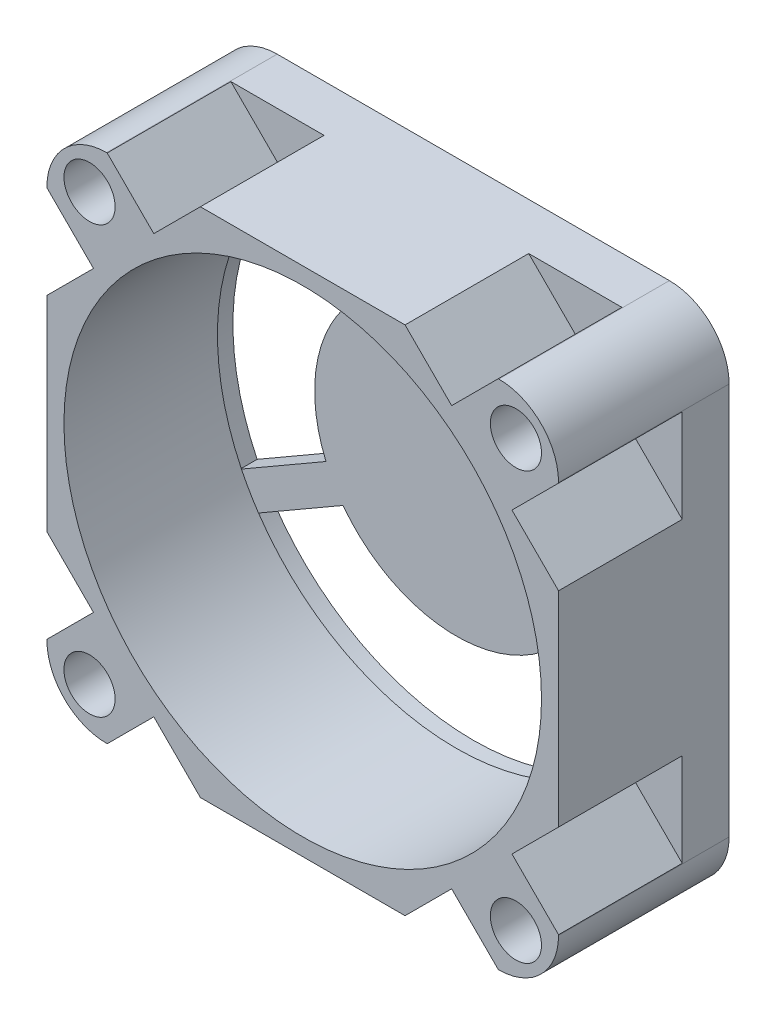
SolidWorks part; units mm, degrees
ref_plane "Płaszczyzna przednia" through (0, 0, 0) normal (0, 0, 1) x (1, 0, 0)
ref_plane "Płaszczyzna górna" through (0, 0, 0) normal (0, 1, 0) x (1, 0, 0)
ref_plane "Płaszczyzna prawa" through (0, 0, 0) normal (1, 0, 0) x (0, 0, -1)
sketch "Sketch1" plane through (0, 0, 0) normal (0, 0, 1) x (1, 0, 0)
  line L1 (0, 0) -> (30, 0)
  line L2 (0, 0) -> (0, 30)
  line L3 (0, 30) -> (30, 30)
  line L4 (30, 0) -> (30, 30)
  dimension "D1" = 30
extrude "Boss-Extrude1" add sketch "Sketch1" along normal blind 10
sketch "Sketch2" plane through (0, 0, 10) normal (0, 0, 1) x (1, 0, 0)
  line L0 (0, 30) -> (30, 0) construction
  line L1 (0, 0) -> (30, 30) construction
  circle A0 centre (15, 15) radius 14
  point P11 (15, 15)
  dimension "D1" = 28
extrude "Cut-Extrude1" cut sketch "Sketch2" against normal blind 9
sketch "Sketch3" plane through (0, 0, 1) normal (0, 0, 1) x (1, 0, 0)
  line L0 (14, 23.2395) -> (14, 29.0554)
  line L1 (16, 23.2395) -> (16, 29.0554)
  line L2 (22.6356, 11.7463) -> (27.6724, 8.8383)
  line L3 (21.6356, 10.0142) -> (26.6724, 7.1063)
  line L4 (8.3644, 10.0142) -> (3.3276, 7.1063)
  line L5 (7.3644, 11.7463) -> (2.3276, 8.8383)
  line L8 (0, 30) -> (0, 0) construction
  line L9 (30, 0) -> (30, 30) construction
  arc A0 (3.3276, 7.1063) -> (26.6724, 7.1063) centre (15, 15) ccw
  arc A1 (8.3644, 10.0142) -> (21.6356, 10.0142) centre (15, 15) ccw
  arc A2 (14, 23.2395) -> (7.3644, 11.7463) centre (15, 15) ccw
  arc A3 (14, 29.0554) -> (2.3276, 8.8383) centre (15, 15) ccw
  arc A4 (22.6356, 11.7463) -> (16, 23.2395) centre (15, 15) ccw
  arc A5 (27.6724, 8.8383) -> (16, 29.0554) centre (15, 15) ccw
  dimension "D1" = 16.6
  dimension "D2" = 2
  dimension "D4" = 14
  dimension "D5" = 14
  dimension "D3" = 3
extrude "Cut-Extrude2" cut sketch "Sketch3" against normal through all
hole_wizard "Ø3.0mm Dowel Hole1" positions "Sketch4" profile "Sketch5" hole size "Ø3.0" standard "ANSI Metric" end condition through all
sketch "Sketch4" plane through (0, 0, 0) normal (0, 0, -1) x (-1, 0, 0)
  line L0 (-30, 0) -> (-30, 30) construction
  line L2 (-30, 30) -> (0, 30) construction
  point P0 (-27.5, 27.5)
  point P19 (-2.5, 27.5)
  point P20 (-2.5, 2.5)
  point P21 (-27.5, 2.5)
  dimension "D1" = 2.5
  dimension "D2" = 2.5
  dimension "D3" = 4
sketch "Sketch5" plane through (27.5, 27.5, 0) normal (1, 0, 0) x (0, 1, 0)
  line L0 (0, 0) -> (0, 10)
  line L1 (0, 10) -> (1.5, 10)
  line L2 (1.5, 10) -> (1.5, 0)
  line L5 (1.5, 0) -> (0, 0)
  line L11 (0, -6.35) -> (0, 107.95) construction
  dimension "Thru Hole Dia." = 3
  dimension "Thru Hole Depth" = 10
sketch "Sketch6" plane through (0, 0, 10) normal (0, 0, 1) x (1, 0, 0)
  line L0 (9, 30) -> (6.2678, 27.2678)
  line L1 (30, 30) -> (0, 30) construction
  line L2 (6.2678, 27.2678) -> (3.5355, 30)
  line L3 (15, 30) -> (15, 0) construction
  line L4 (0, 0) -> (30, 0) construction
  line L5 (23.7322, 27.2678) -> (26.4645, 30)
  line L6 (21, 30) -> (23.7322, 27.2678)
  line L7 (3.5355, 30) -> (9, 30)
  line L8 (21, 30) -> (26.4645, 30)
  line L9 (30, 26.4645) -> (30, 21)
  line L10 (30, 21) -> (27.2678, 23.7322)
  line L11 (27.2678, 23.7322) -> (30, 26.4645)
  line L12 (30, 9) -> (30, 3.5355)
  line L13 (27.2678, 6.2678) -> (30, 3.5355)
  line L14 (30, 9) -> (27.2678, 6.2678)
  line L15 (26.4645, 0) -> (21, 0)
  line L16 (21, 0) -> (23.7322, 2.7322)
  line L17 (23.7322, 2.7322) -> (26.4645, 0)
  line L18 (9, 0) -> (3.5355, 0)
  line L19 (6.2678, 2.7322) -> (3.5355, 0)
  line L20 (9, 0) -> (6.2678, 2.7322)
  line L21 (0, 3.5355) -> (0, 9)
  line L22 (0, 9) -> (2.7322, 6.2678)
  line L23 (2.7322, 6.2678) -> (0, 3.5355)
  line L24 (0, 21) -> (0, 26.4645)
  line L25 (2.7322, 23.7322) -> (0, 26.4645)
  line L26 (0, 21) -> (2.7322, 23.7322)
  circle A0 centre (2.5, 27.5) radius 1.5 construction
  dimension "D3" = 4
  dimension "D1" = 2.5
  dimension "D2" = 12
extrude "Cut-Extrude3" cut sketch "Sketch6" against normal blind 7.25
fillet "Fillet1" radius 3.5 4 edges at (30, 30, 5) (30, 0, 5) (0, 0, 5) (0, 30, 5)
